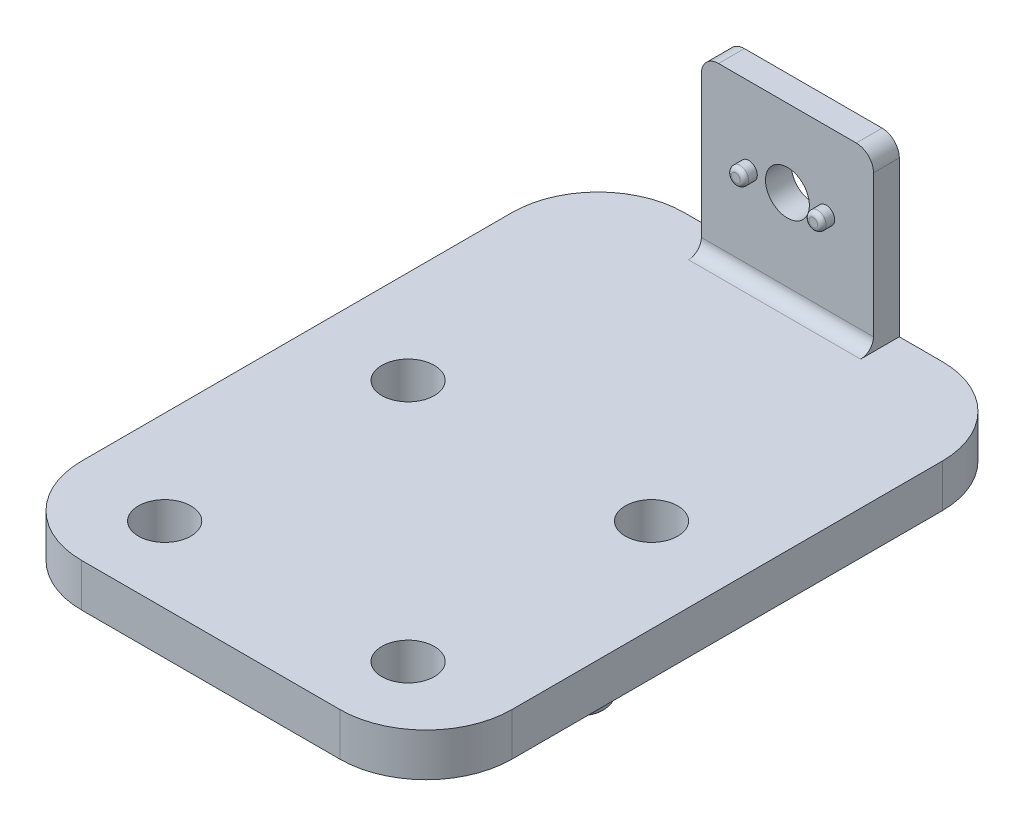
SolidWorks part; units mm, degrees
ref_plane "前视基准面" through (0, 0, 0) normal (0, 0, 1) x (1, 0, 0)
ref_plane "上视基准面" through (0, 0, 0) normal (0, 1, 0) x (1, 0, 0)
ref_plane "右视基准面" through (0, 0, 0) normal (1, 0, 0) x (0, 0, -1)
other "Configuration Table"
sketch "草图1" plane through (0, 0, 0) normal (0, 1, 0) x (1, 0, 0)
  line L0 (-31.7667, 22.0722) -> (83.2558, 22.0722) construction
  line L1 (0, 50.7018) -> (0, -42.4969) construction
  line L3 (-25, 47.0722) -> (25, 47.0722)
  line L4 (-25, 47.0722) -> (-25, -22.9278)
  line L5 (-25, -22.9278) -> (25, -22.9278)
  line L6 (25, 47.0722) -> (25, -22.9278)
  dimension "D1" = 70
  dimension "D2" = 50
  dimension "D3" = 25
  dimension "D4" = 25
extrude "凸台-拉伸1" add sketch "草图1" along normal blind 5
sketch "草图2" plane through (0, 5, 0) normal (0, 1, 0) x (1, 0, 0)
  line L0 (0, 0) -> (22.3212, 0) construction
  line L1 (14.1421, 14.1421) -> (0, 0) construction
  circle A1 centre (14.1421, 14.1421) radius 3.05
  circle A4 centre (14.1421, -14.1421) radius 3.05
  circle A5 centre (-14.1421, -14.1421) radius 3.05
  circle A6 centre (-14.1421, 14.1421) radius 3.05
  point P13 (0, 0)
  dimension "D1" = 4
  dimension "D2" = 20
  dimension "D3" = 45
extrude "切除-拉伸1" cut sketch "草图2" against normal through all contours A6 | A1 | A5 | A4 region at (14.1421, 5, -14.1421) region at (-14.1421, 5, -14.1421)
sketch "草图4" plane through (0, 0, 0) normal (0, -1, 0) x (1, 0, 0)
  line L0 (0, 0) -> (20, 0) construction
  circle A0 centre (20, 0) radius 2.95
  circle A1 centre (-20, 0) radius 2.95
  dimension "D1" = 20
  dimension "D2" = 2
extrude "凸台-拉伸2" add sketch "草图4" along normal blind 3
fillet "圆角1" radius 1 2 edges at (-20, -3, -2.95) (20, -3, -2.95)
sketch "草图6" plane through (0, 5, 0) normal (0, 1, 0) x (1, 0, 0)
  line L0 (-37.4427, 0) -> (40.1246, 0) construction
  line L1 (0, 26.6122) -> (0, -27.6953) construction
  line L3 (-10, 47.0722) -> (10, 47.0722)
  line L4 (-10, 47.0722) -> (-10, 44.0722)
  line L5 (-10, 44.0722) -> (10, 44.0722)
  line L6 (10, 47.0722) -> (10, 44.0722)
  line L7 (25, 47.0722) -> (-25, 47.0722) construction
  point P9 (-10, 45.5722)
  dimension "D1" = 20
  dimension "D2" = 10
  dimension "D3" = 3
fillet "圆角2" radius 10 4 edges at (-25, 2.5, -47.0722) (25, 2.5, -47.0722) (-25, 2.5, 22.9278) (25, 2.5, 22.9278)
extrude "凸台-拉伸3" add sketch "草图6" along normal blind 20
sketch "草图8" plane through (-10, 0, 0) normal (-1, 0, 0) x (0, 0, 1)
  line L0 (-44.0722, 25) -> (-44.0722, 5) construction
  line L1 (-47.0722, 5) -> (-44.0722, 5) construction
  line L2 (-44.0722, 6.5) -> (-44.0722, 5)
  line L3 (-44.0722, 5) -> (-42.5722, 5)
  arc A0 (-42.5722, 5) -> (-44.0722, 6.5) centre (-42.5722, 6.5) cw
  dimension "D1" = 1.5
  dimension "D2" = 1.5
extrude "凸台-拉伸5" add sketch "草图8" against normal blind 20
fillet "圆角3" radius 2 2 edges at (-10, 25, -45.5722) (10, 25, -45.5722)
sketch "草图9" plane through (0, 0, -44.0722) normal (0, 0, 1) x (1, 0, 0)
  line L0 (-10, 23) -> (-10, 6.5) construction
  line L1 (-8, 25) -> (8, 25) construction
  line L2 (0, 16) -> (-10.7913, 16) construction
  line L3 (0, 16) -> (12.3956, 16) construction
  line L4 (0, 16) -> (0, 24.172) construction
  line L5 (0, 16) -> (0, 9.2776) construction
  circle A0 centre (0, 16) radius 2.55
  circle A1 centre (-4.5, 16) radius 1
  circle A2 centre (4.5, 16) radius 1
  dimension "D1" = 10
  dimension "D3" = 4.5
  dimension "D2" = 9
  dimension "D4" = 2
extrude "切除-拉伸2" cut sketch "草图9" against normal through all contours A0
extrude "凸台-拉伸6" add sketch "草图9<4>" along normal blind 1.5 contours A1 | A2 region at (-4.5, 16, -44.0722) region at (4.5, 16, -44.0722)
sketch "草图9<4>" plane through (0, 0, -44.0722) normal (0, 0, 1) x (1, 0, 0) same geometry as "草图9"
fillet "圆角4" radius 0.5 2 edges at (5.5, 16, -42.5722) (-3.5, 16, -42.5722)
